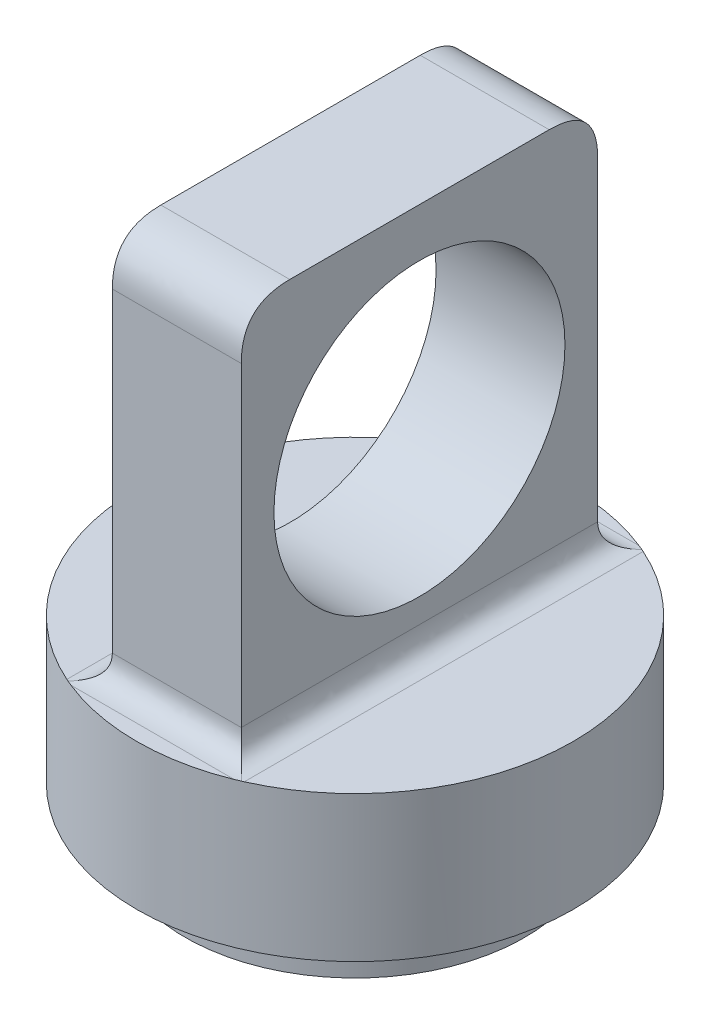
SolidWorks part; units mm, degrees
ref_plane "Front Plane" through (0, 0, 0) normal (0, 0, 1) x (1, 0, 0)
ref_plane "Top Plane" through (0, 0, 0) normal (0, 1, 0) x (1, 0, 0)
ref_plane "Right Plane" through (0, 0, 0) normal (1, 0, 0) x (0, 0, -1)
sketch "Sketch1" plane through (0, 0, 0) normal (0, 1, 0) x (1, 0, 0)
  circle A0 centre (0, 0) radius 114.3
  dimension "D1" = 228.6
extrude "Boss-Extrude1" add sketch "Sketch1" along normal blind 76.2
sketch "Sketch2" plane through (0, 0, 0) normal (0, -1, 0) x (-1, 0, 0)
  circle A0 centre (0, 0) radius 88.9
extrude "Boss-Extrude2" add sketch "Sketch2" along normal blind 25.4
sketch "Sketch3" plane through (0, 76.2, 0) normal (0, 1, 0) x (1, 0, 0)
  line L1 (-33.7518, 93.3144) -> (33.7518, 93.3144)
  line L2 (-33.7518, 93.3144) -> (-33.7518, -93.3144)
  line L3 (-33.7518, -93.3144) -> (33.7518, -93.3144)
  line L4 (33.7518, 93.3144) -> (33.7518, -93.3144)
  line L6 (0, 0) -> (-117.0658, 0) construction
  line L7 (0, 0) -> (0, 142.2125) construction
  point P8 (0, 0)
extrude "Boss-Extrude3" add sketch "Sketch3" along normal blind 203.2
sketch "Sketch4" plane through (-33.7518, 0, 0) normal (-1, 0, 0) x (0, 0, 1)
  line L0 (93.3144, 279.4) -> (-93.3144, 76.2) construction
  line L1 (-93.3144, 279.4) -> (93.3144, 76.2) construction
  circle A0 centre (0, 177.8) radius 76.2
  dimension "D1" = 152.4
extrude "Cut-Extrude1" cut sketch "Sketch4" against normal blind 127
fillet "Fillet1" radius 25.4 2 edges at (0, 279.4, 93.3144) (0, 279.4, -93.3144) conic rho 0.5
fillet "Fillet2" radius 12.7 4 edges at (0, 76.2, 93.3144) (0, 76.2, -93.3144) (-33.7518, 76.2, 0) (33.7518, 76.2, 0) conic rho 0.5
